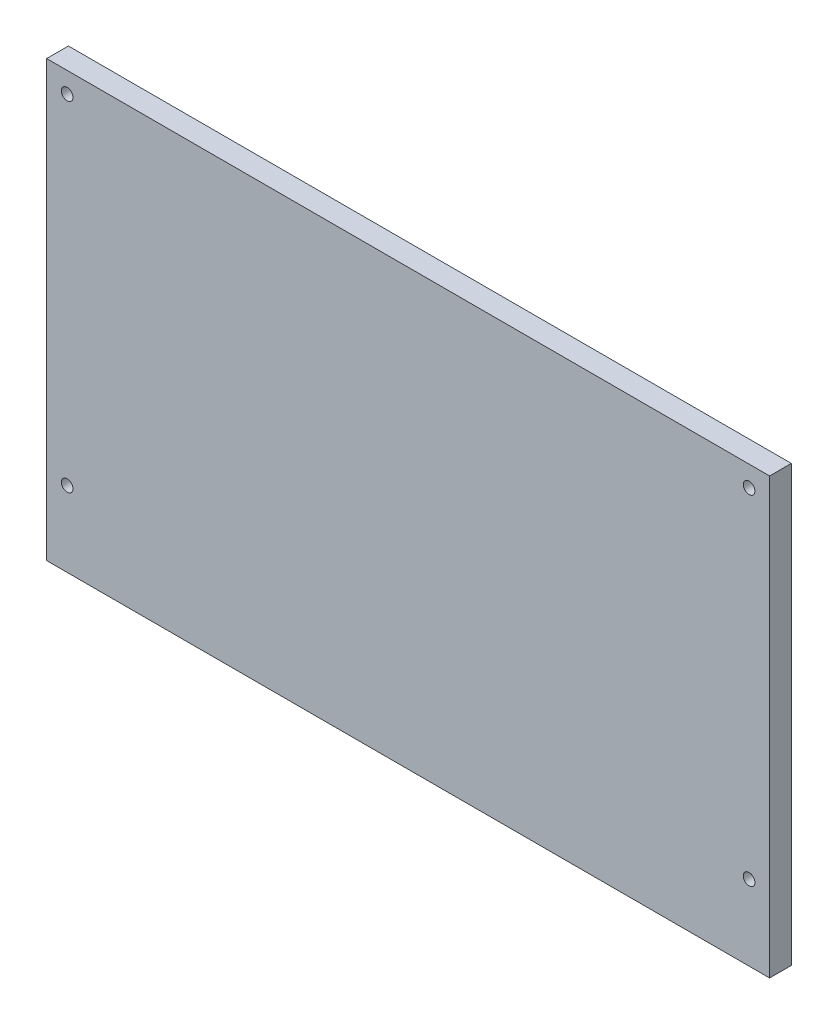
SolidWorks part; units mm, degrees
material "Acrylic (Medium-high impact)"
ref_plane "Front Plane" through (0, 0, 0) normal (0, 0, 1) x (1, 0, 0)
ref_plane "Top Plane" through (0, 0, 0) normal (0, 1, 0) x (1, 0, 0)
ref_plane "Right Plane" through (0, 0, 0) normal (1, 0, 0) x (0, 0, -1)
sketch "Sketch1" plane through (0, 0, 0) normal (0, 0, 1) x (1, 0, 0)
  line L1 (211.1756, 127) -> (0, 127)
  line L2 (211.1756, 127) -> (211.1756, 0)
  line L3 (211.1756, 0) -> (0, 0)
  line L4 (0, 127) -> (0, 0)
  line L5 (211.1756, 127) -> (0, 0) construction
  line L6 (211.1756, 0) -> (0, 127) construction
  point P0 (105.5878, 63.5)
  dimension "D1" = 127
  dimension "D2" = 211.1756
extrude "Boss-Extrude1" add sketch "Sketch1" along normal blind 6.35
hole_wizard "M3 Clearance Hole1" positions "Sketch2" profile "Sketch3" hole size "M3" standard "ANSI Metric" end condition through all
sketch "Sketch2" plane through (0, 0, 6.35) normal (0, 0, 1) x (1, 0, 0)
  line L0 (0, 127) -> (0, 0) construction
  line L1 (211.1756, 127) -> (0, 127) construction
  line L2 (211.1756, 0) -> (211.1756, 127) construction
  line L3 (0, 0) -> (211.1756, 0) construction
  point P0 (5.9944, 121.0056)
  point P2 (5.9944, 21.9964)
  point P4 (205.1812, 21.9964)
  point P6 (205.1812, 121.0056)
  point P29 (0, 0)
  dimension "D1" = 5.9944
  dimension "D2" = 5.9944
  dimension "D3" = 5.9944
  dimension "D4" = 21.9964
sketch "Sketch3" plane through (5.9944, 121.0056, 6.35) normal (1, 0, 0) x (0, -1, 0)
  line L0 (0, 0) -> (0, 6.35)
  line L1 (0, 6.35) -> (1.7, 6.35)
  line L2 (1.7, 6.35) -> (1.7, 0)
  line L5 (1.7, 0) -> (0, 0)
  line L11 (0, -6.35) -> (0, 107.95) construction
  dimension "Thru Hole Dia." = 3.4
  dimension "Thru Hole Depth" = 6.35
sketch "Sketch4" plane through (0, 0, 6.35) normal (0, 0, 1) x (1, 0, 0)
  line L0 (0, 127) -> (0, 0) construction
  line L1 (46.99, 107.95) -> (50.4952, 107.95)
  line L2 (46.99, 107.95) -> (46.99, 44.45)
  line L3 (46.99, 44.45) -> (50.4952, 44.45)
  line L4 (50.4952, 107.95) -> (50.4952, 44.45)
  line L5 (160.6804, 107.95) -> (164.1856, 107.95)
  line L6 (160.6804, 107.95) -> (160.6804, 44.45)
  line L7 (160.6804, 44.45) -> (164.1856, 44.45)
  line L8 (164.1856, 107.95) -> (164.1856, 44.45)
  line L9 (211.1756, 0) -> (211.1756, 127) construction
  line L10 (211.1756, 127) -> (0, 127) construction
  dimension "D1" = 3.5052
  dimension "D2" = 63.5
  dimension "D3" = 46.99
  dimension "D4" = 46.99
  dimension "D5" = 19.05
extrude "Cut-Extrude1" [suppressed] cut sketch "Sketch4" against normal through all
sketch "Sketch5" plane through (0, 0, 6.35) normal (0, 0, 1) x (1, 0, 0)
  line L0 (0, 10.7092) -> (76.2, 0)
  line L1 (0, 127) -> (0, 0) construction
  line L2 (0, 0) -> (211.1756, 0) construction
  line L3 (76.2, 0) -> (0, 0)
  line L4 (0, 0) -> (0, 10.7092)
  line L5 (134.9756, 0) -> (211.1756, 0)
  line L6 (211.1756, 0) -> (211.1756, 10.7092)
  line L7 (211.1756, 0) -> (211.1756, 127) construction
  line L8 (211.1756, 10.7092) -> (134.9756, 0)
  dimension "D1" = 8
  dimension "D2" = 8
  dimension "D3" = 76.2
  dimension "D4" = 76.2
extrude "Cut-Extrude2" [suppressed] cut sketch "Sketch5" against normal through all
